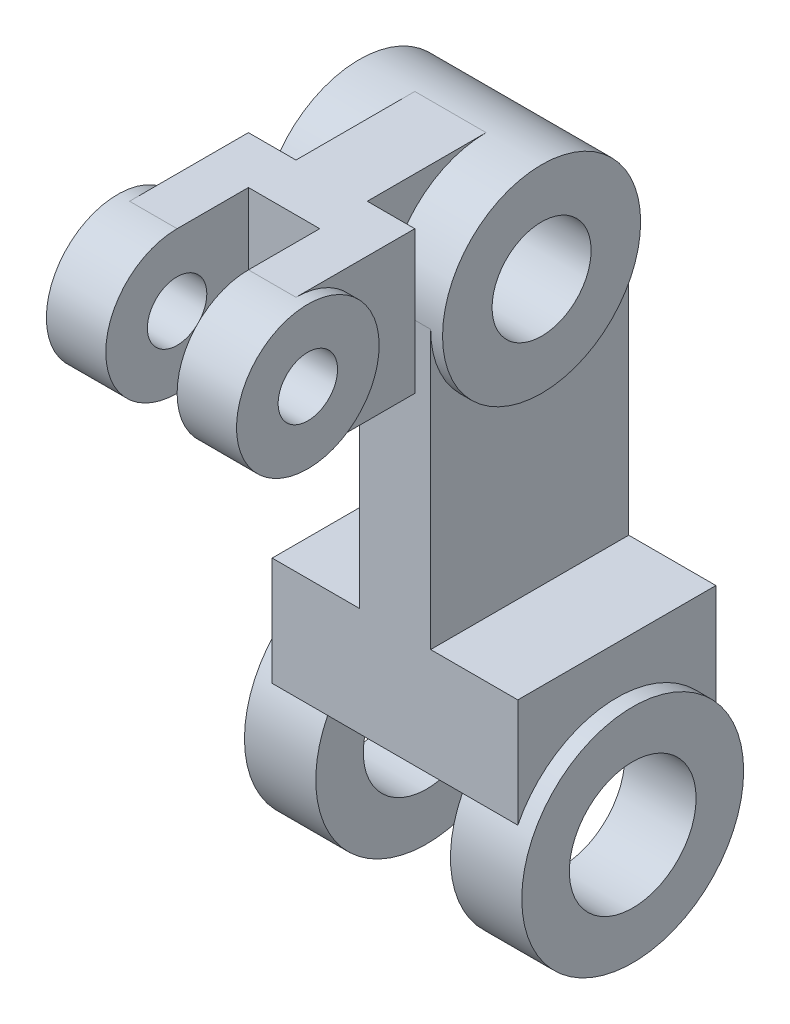
SolidWorks part; units mm, degrees
ref_plane "Front Plane" through (0, 0, 0) normal (0, 0, 1) x (1, 0, 0)
ref_plane "Top Plane" through (0, 0, 0) normal (0, 1, 0) x (1, 0, 0)
ref_plane "Right Plane" through (0, 0, 0) normal (1, 0, 0) x (0, 0, -1)
sketch "Sketch2" plane through (0, 0, 0) normal (0, 0, 1) x (1, 0, 0)
  line L0 (0, -48.0566) -> (0, 100.4746) construction
  line L1 (-1, -32.434) -> (31, -32.434)
  line L2 (31, -32.434) -> (31, 35.566)
  line L3 (31, 35.566) -> (9, 35.566)
  line L4 (9, 35.566) -> (9, 80.566)
  line L5 (9, 80.566) -> (12, 80.566)
  line L6 (12, 80.566) -> (12, 130.566)
  line L7 (12, 130.566) -> (0, 130.566)
  line L8 (-1, -32.434) -> (-31, -32.434)
  line L9 (-31, -32.434) -> (-31, 35.566)
  line L10 (-31, 35.566) -> (-9, 35.566)
  line L11 (-9, 35.566) -> (-9, 80.566)
  line L12 (0, 130.566) -> (-34, 130.566)
  line L13 (-34, 130.566) -> (-34, 80.566)
  line L14 (-34, 80.566) -> (-9, 80.566)
  dimension "D1" = 32
  dimension "D2" = 68
  dimension "D3" = 9
  dimension "D4" = 3
  dimension "D5" = 50
  dimension "D6" = 45
  dimension "D7" = 46
  dimension "D8" = 30
  dimension "D9" = 30
extrude "Boss-Extrude1" add sketch "Sketch2" along normal mid plane 50
sketch "Sketch3" plane through (31, 0, 0) normal (1, 0, 0) x (0, 0, -1)
  line L0 (-25, -32.434) -> (25, -32.434) construction
  line L1 (-28, -4.434) -> (-30.642, -47.1116)
  line L2 (-30.642, -47.1116) -> (44.7613, -47.1116)
  line L3 (44.7613, -47.1116) -> (28, -4.434)
  line L4 (-25, 105.566) -> (-43.6234, 147.7484)
  line L5 (-43.6234, 147.7484) -> (44.7613, 142.4731)
  line L6 (44.7613, 142.4731) -> (25, 105.566)
  line L7 (-25, 130.566) -> (25, 130.566) construction
  arc A0 (28, -4.434) -> (-28, -4.434) centre (0, -4.434) ccw
  arc A1 (25, 105.566) -> (-25, 105.566) centre (0, 105.566) ccw
  dimension "D1" = 56
  dimension "D2" = 50
extrude "Cut-Extrude1" cut sketch "Sketch3" against normal through all
sketch "Sketch4" plane through (12, 0, 0) normal (1, 0, 0) x (0, 0, -1)
  circle A0 centre (0, 105.566) radius 25
  arc A1 (25, 105.566) -> (-25, 105.566) centre (0, 105.566) ccw construction
  dimension "D1" = 50
sketch "Sketch5" plane through (12, 0, 0) normal (1, 0, 0) x (0, 0, -1)
  line L0 (-25, 105.566) -> (-25, 80.566)
  line L1 (-25, 80.566) -> (25, 80.566)
  line L2 (25, 80.566) -> (25, 105.566)
  arc A0 (-25, 105.566) -> (25, 105.566) centre (0, 105.566) ccw
  line M2 (25, 80.566) -> (25, 105.566)
  line M4 (-25, 105.566) -> (-25, 80.566)
  line M5 (-25, 80.566) -> (25, 80.566)
  dimension "D1" = 50
extrude "Cut-Extrude9" cut sketch "Sketch5" against normal blind 3 contours A0 L1 M2 | A0 M4 M5 region at (12, 86.1502, 19.4158) region at (12, 86.1502, -19.4158)
sketch "Sketch6" plane through (-34, 0, 0) normal (-1, 0, 0) x (0, 0, 1)
  line L0 (25, 80.566) -> (-25, 80.566) construction
  line L1 (25, 105.566) -> (25, 80.566) construction
  line L2 (-25, 105.566) -> (-25, 80.566)
  line L3 (-25, 80.566) -> (25, 80.566)
  line L4 (25, 80.566) -> (25, 105.566)
  circle A0 centre (0, 105.566) radius 25
  circle A1 centre (0, 105.566) radius 12.5
  line M1 (25, 80.566) -> (25, 105.566)
  line M3 (-25, 105.566) -> (-25, 80.566)
  line M4 (-25, 80.566) -> (25, 80.566)
  dimension "D1" = 50
  dimension "D2" = 25
extrude "Cut-Extrude10" cut sketch "Sketch6" along normal through all from surface contours A0 L3 M1 | A0 M3 M4 region at (-34, 86.1502, -19.4158) region at (-34, 86.1502, 19.4158) starting at face at (-9, 58.066, 0)
extrude "Cut-Extrude11" cut sketch "Sketch6<3>" against normal through all contours A1
sketch "Sketch6<3>" plane through (-34, 0, 0) normal (-1, 0, 0) x (0, 0, 1) same geometry as "Sketch6"
sketch "Sketch7" plane through (31, 0, 0) normal (1, 0, 0) x (0, 0, -1)
  circle A0 centre (0, -4.434) radius 28
  arc A1 (25, 8.1756) -> (-25, 8.1756) centre (0, -4.434) ccw construction
  circle A2 centre (0, -4.434) radius 16
  dimension "D1" = 56
  dimension "D2" = 32
extrude "Boss-Extrude2" add sketch "Sketch7" along normal blind 4 and the other way blind 14
pattern_linear "LPattern1" count 2 spacing 52 along (-1, 0, 0) of "Boss-Extrude2"
ref_plane "Plane1" through (0, 130.566, 0) normal (0, 1, 0) x (1, 0, 0)
sketch "Sketch8" plane through (0, 130.566, 0) normal (0, 1, 0) x (1, 0, 0)
  line L0 (-11, 48.9964) -> (-11, -117.7514) construction
  line L1 (-34, 25) -> (-34, -25) construction
  line L2 (-20, 0) -> (-2, 0)
  line L3 (-2, -78) -> (-2, -42)
  line L4 (13, -78) -> (-2, -78)
  line L5 (13, -42) -> (13, -78)
  line L6 (10, -42) -> (13, -42)
  line L7 (10, -30) -> (10, -42)
  line L8 (10, -30) -> (-2, -30)
  line L9 (-2, 0) -> (-2, -30)
  line L11 (-20, 0) -> (-20, -30)
  line L13 (-32, -30) -> (-32, -42)
  line L14 (-32, -30) -> (-20, -30)
  line L15 (-32, -42) -> (-35, -42)
  line L16 (-35, -42) -> (-35, -78)
  line L17 (-35, -78) -> (-20, -78)
  line L18 (-20, -78) -> (-20, -42)
  line L19 (-20, -42) -> (-2, -42)
  point P2 (-27.5, -78)
  point P18 (-11, 0)
  point P19 (-11, -42)
  dimension "D1" = 23
  dimension "D2" = 12
  dimension "D3" = 48
  dimension "D4" = 15
  dimension "9" = 9
  dimension "D5" = 36
  dimension "D6" = 9
  dimension "D7" = 36
  dimension "D8" = 30
extrude "Boss-Extrude3" add sketch "Sketch8" against normal blind 36
sketch "Sketch9" plane through (-34, 0, 0) normal (-1, 0, 0) x (0, 0, 1)
  circle A0 centre (0, 105.566) radius 12.5
extrude "Cut-Extrude12" cut sketch "Sketch9" against normal through all
sketch "Sketch10" plane through (-35, 0, 0) normal (-1, 0, 0) x (0, 0, 1)
  line L1 (42, 94.566) -> (78, 94.566) construction
  line L2 (78, 94.566) -> (78, 130.566) construction
  line L4 (60, 94.566) -> (99.5794, 93.2223)
  line L5 (99.5794, 93.2223) -> (99.5794, 133.58)
  line L6 (99.5794, 133.58) -> (60, 130.566)
  arc A0 (60, 94.566) -> (60, 130.566) centre (60, 112.566) ccw
  dimension "D1" = 36
extrude "Cut-Extrude13" cut sketch "Sketch10" against normal through all
sketch "Sketch11" plane through (-35, 0, 0) normal (-1, 0, 0) x (0, 0, 1)
  line L0 (60, 130.566) -> (34.9884, 136.0584)
  line L1 (34.9884, 136.0584) -> (42, 90.4903)
  line L2 (42, 90.4903) -> (60, 94.566)
  arc A0 (60, 130.566) -> (60, 94.566) centre (60, 112.566) ccw
  dimension "D1" = 36
extrude "Cut-Extrude14" cut sketch "Sketch11" against normal blind 3
pattern_linear "LPattern2" count 2 spacing 45 along (1, 0, 0) of "Cut-Extrude14"
sketch "Sketch12" plane through (-35, 0, 0) normal (-1, 0, 0) x (0, 0, 1)
  circle A0 centre (60, 112.566) radius 7.5
  circle A1 centre (60, 112.566) radius 18 construction
  dimension "D1" = 15
extrude "Cut-Extrude15" cut sketch "Sketch12" against normal through all
